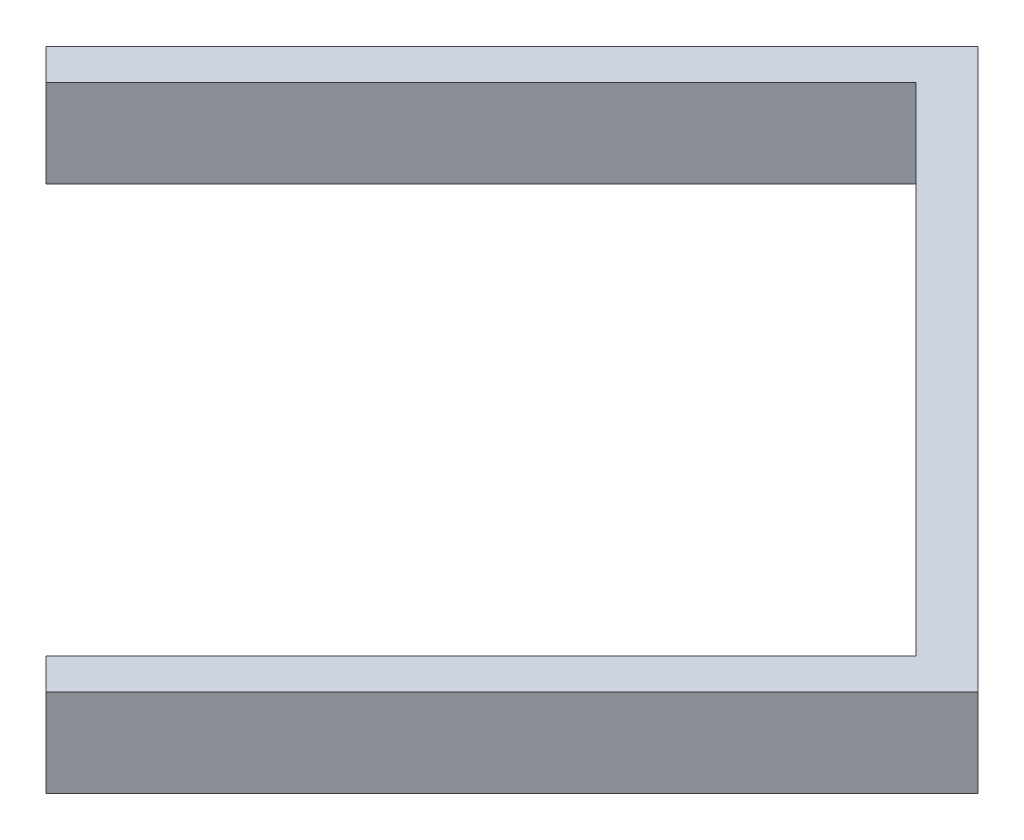
SolidWorks part; units mm, degrees
ref_plane "Front Plane" through (0, 0, 0) normal (0, 0, 1) x (1, 0, 0)
ref_plane "Top Plane" through (0, 0, 0) normal (0, 1, 0) x (1, 0, 0)
ref_plane "Right Plane" through (0, 0, 0) normal (1, 0, 0) x (0, 0, -1)
sketch "Sketch2" plane through (0, 0, 0) normal (0, 1, 0) x (1, 0, 0)
  line L0 (-311.9853, 47.8058) -> (-329.9458, 65.7663)
  line L1 (-329.9458, 65.7663) -> (-60.5382, 335.174)
  line L2 (-60.5382, 335.174) -> (262.7511, 11.8848)
  line L3 (262.7511, 11.8848) -> (-6.6566, -257.5229)
  line L4 (-6.6566, -257.5229) -> (-24.6171, -239.5624)
  line L5 (-24.6171, -239.5624) -> (226.83, 11.8848)
  line L6 (226.83, 11.8848) -> (-60.5382, 299.253)
  line L7 (-60.5382, 299.253) -> (-311.9853, 47.8058)
  line L8 (-154.8004, -82.3774) -> (83.1459, 155.5689)
  point P10 (83.1459, 155.5689)
  dimension "D1" = 25.4
  dimension "D2" = 25.4
  dimension "D3" = 406.4
  dimension "D4" = 355.6
extrude "Boss-Extrude2" add sketch "Sketch2" along normal blind 50.8 contours L7 L6 L5 L4 L3 L2 L1 L0 region at (-315.0386, 0, -62.7131)
sketch "Sketch3" plane through (137.3179, 0, -137.3179) normal (0.7071, 0, -0.7071) x (-0.7071, 0, -0.7071)
  line L0 (279.8108, 50.8) -> (279.8108, 0) construction
  circle A0 centre (0, 25.4) radius 6.35
  point P5 (279.8108, 25.4)
  dimension "D1" = 12.7
extrude "Cut-Extrude1" cut sketch "Sketch3" against normal blind 50.8
